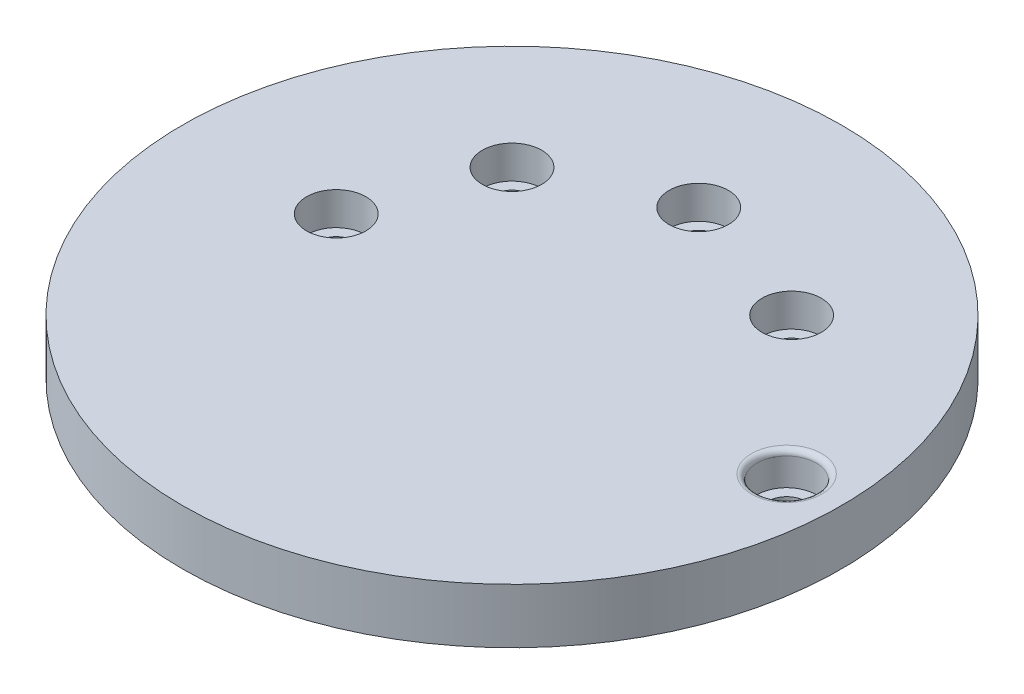
SolidWorks part; units mm, degrees
ref_plane "Front Plane" through (0, 0, 0) normal (0, 0, 1) x (1, 0, 0)
ref_plane "Top Plane" through (0, 0, 0) normal (0, 1, 0) x (1, 0, 0)
ref_plane "Right Plane" through (0, 0, 0) normal (1, 0, 0) x (0, 0, -1)
sketch "Sketch1" plane through (0, 0, 0) normal (0, 1, 0) x (1, 0, 0)
  line L0 (-1.7864, 2.4875) -> (1.7864, 2.4875)
  circle A0 centre (0, 0) radius 38.1
  arc A1 (-1.7864, 2.4875) -> (1.7864, 2.4875) centre (0, 0) ccw
  dimension "D1" = 76.2
  dimension "D2" = 6.125
  dimension "D3" = 3.5728
extrude "Boss-Extrude1" add sketch "Sketch1" along normal blind 6.35
sketch "Sketch2" plane through (0, 6.35, 0) normal (0, 1, 0) x (1, 0, 0)
  line L1 (0, 0) -> (-20.32, 0)
  line L2 (0, 0) -> (-14.8174, 14.8174)
  line L3 (0, 0) -> (0, 21.59)
  line L4 (0, 0) -> (16.1645, 16.1645)
  line L5 (0, 0) -> (19.63, 0)
  circle A0 centre (31.75, 0) radius 3.429
  circle A1 centre (31.75, 0) radius 2.159
  circle A2 centre (-20.32, 0) radius 3.429
  circle A3 centre (-20.32, 0) radius 2.159
  circle A4 centre (-14.8174, 14.8174) radius 3.429
  circle A5 centre (-14.8174, 14.8174) radius 2.159
  circle A6 centre (0, 21.59) radius 3.429
  circle A7 centre (0, 21.59) radius 2.159
  circle A8 centre (16.1645, 16.1645) radius 3.429
  circle A9 centre (16.1645, 16.1645) radius 2.159
  dimension "D1" = 6.858
  dimension "D3" = 4.318
  dimension "D2" = 31.75
  dimension "D4" = 22.86
  dimension "D5" = 21.59
  dimension "D6" = 20.955
  dimension "D7" = 20.32
  dimension "D8" = 45
  dimension "D9" = 45
  dimension "D10" = 45
  dimension "D11" = 45
extrude "Cut-Extrude1" cut sketch "Sketch2" against normal blind 3.81 and the other way through all contours A1 | A0 A1 | A9 A8 | A9 | A7 A6 | A7 | A3 A2 | A3 | A5 A4 | A5 region at (-22.4179, 6.35, 0) region at (-23.652, 6.35, 0) region at (-16.7557, 6.35, -15.6203) region at (-17.8958, 6.35, -16.0925) region at (-1.4835, 6.35, -23.0735) region at (-2.3561, 6.35, -23.9461) region at (15.3616, 6.35, -18.1027) region at (14.8894, 6.35, -19.2428) region at (28.418, 6.35, 0) region at (31.75, 6.35, 0)
extrude "Cut-Extrude2" cut sketch "Sketch2<3>" against normal through all both and the other way through all contours A1 | A3 | A5 | A7 | A9 region at (-22.4179, 6.35, 0) region at (-16.7557, 6.35, -15.6203) region at (-1.4835, 6.35, -23.0735) region at (15.3616, 6.35, -18.1027) region at (31.75, 6.35, 0)
sketch "Sketch2<3>" plane through (0, 6.35, 0) normal (0, 1, 0) x (1, 0, 0) same geometry as "Sketch2"
sketch "Sketch4" plane through (0, 6.35, 0) normal (0, 1, 0) x (1, 0, 0)
  circle A0 centre (0, 0) radius 6.9106
extrude "Boss-Extrude2" add sketch "Sketch4" against normal blind 1.27
sketch "Sketch5" plane through (0, 0, 0) normal (0, -1, 0) x (1, 0, 0)
  line L2 (-1.7864, -2.4875) -> (1.7864, -2.4875)
  line L3 (-1.7864, -2.4875) -> (1.7864, -2.4875)
  circle A1 centre (0, 0) radius 6.35
  arc A2 (1.7864, -2.4875) -> (-1.7864, -2.4875) centre (0, 0) ccw
  arc A3 (1.7864, -2.4875) -> (-1.7864, -2.4875) centre (0, 0) ccw
  dimension "D1" = 0
extrude "Boss-Extrude3" add sketch "Sketch5" along normal blind 3.81
fillet "Fillet1" radius 3.81 1 edges at (0, 0, 6.35)
fillet "Fillet2" radius 0.635 1 edges at (31.75, 6.35, 3.429)
